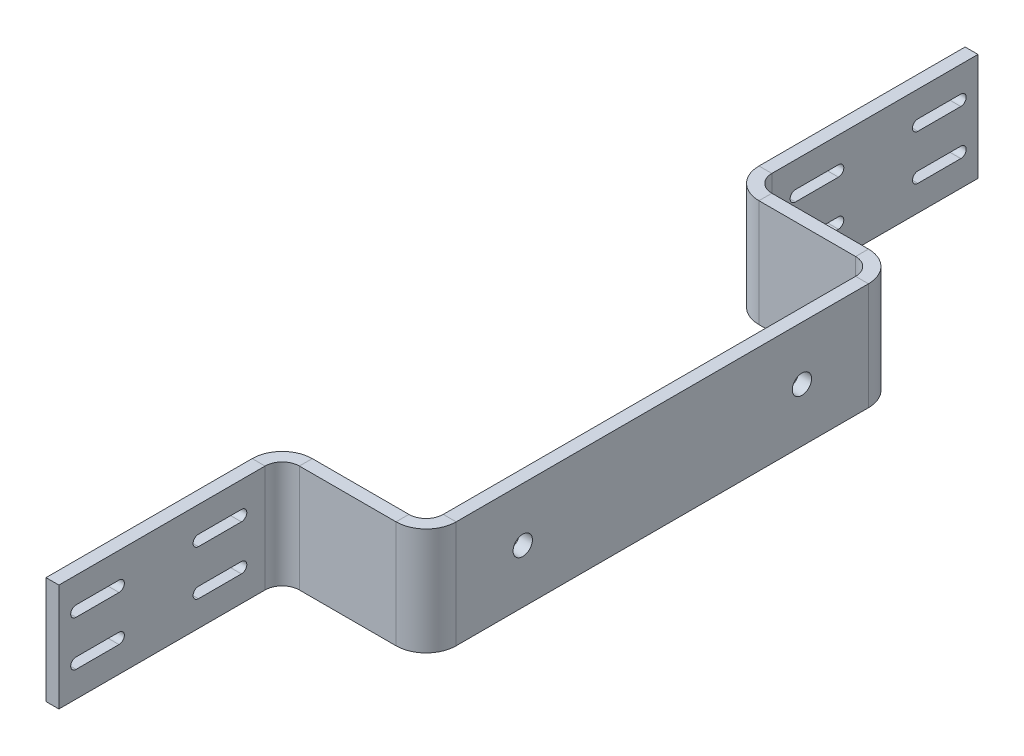
SolidWorks part; units mm, degrees
note: The reader was unsure of these and kept them because the rebuilt part matched: flange length of "Edge-Flange1", "Edge-Flange2".
material "Plain Carbon Steel"
ref_plane "Front Plane" through (0, 0, 0) normal (0, 0, 1) x (1, 0, 0)
ref_plane "Top Plane" through (0, 0, 0) normal (0, 1, 0) x (1, 0, 0)
ref_plane "Right Plane" through (0, 0, 0) normal (1, 0, 0) x (0, 0, -1)
sketch "Sketch1" plane through (0, 0, 0) normal (1, 0, 0) x (0, 0, -1)
  line L1 (-55, -25) -> (55, -25)
  line L2 (-55, -25) -> (-55, 25)
  line L3 (-55, 25) -> (55, 25)
  line L4 (55, -25) -> (55, 25)
  line L5 (-55, -25) -> (55, 25) construction
  line L6 (-55, 25) -> (55, -25) construction
  point P0 (0, 0)
  dimension "D1" = 50
  dimension "D2" = 110
base flange "Base-Flange1" sketch "Sketch1" thickness 6 reverse thickness direction no parameters "D1"=15
sketch "Sketch5" plane through (-6, 0, 0) normal (-1, 0, 0) x (0, 0, 1)
  line L0 (-30, 10.5) -> (-10, 10.5) construction
  line L3 (-30, 13) -> (-10, 13)
  line L4 (-30, 8) -> (-10, 8)
  line L6 (-55, -25) -> (-55, 25) construction
  arc A2 (-30, 13) -> (-30, 8) centre (-30, 10.5) ccw
  arc A3 (-10, 8) -> (-10, 13) centre (-10, 10.5) ccw
  point P2 (-20, 10.5)
  dimension "D1" = 20
  dimension "D2" = 5
  dimension "D3" = 10.5
  dimension "D4" = 25
extrude "Cut-Extrude1" cut sketch "Sketch5" against normal blind 10
pattern_linear "LPattern1" count 2 spacing 57 along (0, 0, 1) of "Cut-Extrude1"
mirror "Mirror1" about plane through (0, 0, 0) normal (0, 1, 0) of "LPattern1", "Cut-Extrude1"
edge flange "Edge-Flange1" sketch "Sketch11" flange angle 90 flange length 73 flange position material inside bend radius 8 thickness 6 relief rectangular parameters "D6"=10
bend "EdgeBend3" bend radius 8 bend angle 90 parameters "D5"=1
sketch "Sketch11" plane through (0, 0, -55) normal (0, 0, -1) x (0, 1, 0)
  line L1 (-25, 0) -> (25, 0) construction
  line L2 (25, 0) -> (25, 67)
  line L3 (25, 67) -> (-25, 67)
  line L4 (-25, 67) -> (-25, 0)
  line L5 (-25, 0) -> (25, 0)
edge flange "Edge-Flange2" sketch "Sketch13" flange angle 90 flange length 110 flange position material inside bend radius 8 thickness 6 relief rectangular parameters "D6"=10
bend "EdgeBend4" bend radius 8 bend angle 90 parameters "D5"=2
sketch "Sketch13" plane through (67, 0, -55) normal (1, 0, 0) x (0, -1, 0)
  line L0 (-25, 0) -> (25, 0) construction
  line L1 (-25, 0) -> (25, 0)
  line L2 (-25, 0) -> (-25, 104)
  line L3 (-25, 104) -> (25, 104)
  line L4 (25, 104) -> (25, 0)
sketch "Sketch9" plane through (61, 0, 0) normal (-1, 0, 0) x (0, 0, 1)
  line L2 (-159, -25) -> (-159, 25) construction
  circle A0 centre (-94, 0) radius 4.5
  dimension "D1" = 9
  dimension "D2" = 65
extrude "Cut-Extrude2" cut sketch "Sketch9" against normal blind 10
ref_plane "Plane1" through (0, 0, -159) normal (0, 0, -1) x (-1, 0, 0)
mirror "Mirror2" about plane through (67, 25, -159) normal (0, 0, 1) of bodies 111
bend "MirrorBend3" bend radius 8 bend angle 90 parameters "D5"=3
bend "MirrorBend4" bend radius 8 bend angle 90 parameters "D5"=4
sketch "Bend-Lines1" [suppressed] plane through (0, 0, 0) normal (0, 1, 0) x (1, 0, 0)
sketch "Bounding-Box1" [suppressed] plane through (0, 0, 0) normal (0, 1, 0) x (1, 0, 0)
sheet metal parameters "Sheet-Metal2" thickness 6 parameters "D1"=15
flat pattern "Flat-Pattern2" [suppressed]
sketch "Bend-Lines2" plane through (0, 0, 0) normal (0, 1, 0) x (1, 0, 0)
sketch3d "Bounding-Box2" [suppressed]
  line L0 (55, -25, 0) -> (-55, -25, 0) construction
  line L1 (55, 25, 0) -> (-55, 25, 0) construction
  line L2 (55, -25, 0) -> (55, 25, 0) construction
  line L3 (-55, -25, 0) -> (-55, 25, 0) construction
sheet metal parameters "Sheet-Metal5" thickness 6 parameters "D1"=15
flat pattern "Flat-Pattern2"
sketch "Bend-Lines2" plane through (0, 0, 0) normal (1, 0, 0) x (0, 0, -1)
  line L2 (48.1372, -25) -> (48.1372, 25) construction
  line L3 (48.1372, -25) -> (48.1372, 25) construction
  point P0 (-48.1372, 25)
  point P1 (-48.1372, -25)
sketch3d "Bounding-Box2" [suppressed]
  line L0 (126.2743, -25, 0) -> (-55, -25, 0) construction
  line L1 (126.2743, 25, 0) -> (-55, 25, 0) construction
  line L2 (126.2743, -25, 0) -> (126.2743, 25, 0) construction
  line L3 (-55, -25, 0) -> (-55, 25, 0) construction
bend of the flat pattern "Flatten-<EdgeBend3>1"
sheet metal parameters "Sheet-Metal7" thickness 6 parameters "D1"=15
flat pattern "Flat-Pattern2"
sketch "Bend-Lines2" plane through (0, 0, 0) normal (1, 0, 0) x (0, 0, -1)
  line L0 (-28.1372, 50) -> (-28.1372, -50) construction
  line L1 (-28.1372, 50) -> (-28.1372, -50) construction
sketch3d "Bounding-Box2" [suppressed]
  line L0 (35, -50, 0) -> (-192.2743, -50, 0) construction
  line L1 (35, 50, 0) -> (-192.2743, 50, 0) construction
  line L2 (35, -50, 0) -> (35, 50, 0) construction
  line L3 (-192.2743, -50, 0) -> (-192.2743, 50, 0) construction
sheet metal parameters "Sheet-Metal8" thickness 6 parameters "D1"=15
flat pattern "Flat-Pattern2"
sketch "Bend-Lines2" plane through (0, 0, 0) normal (1, 0, 0) x (0, 0, -1)
  line L0 (-43.1372, 17.5) -> (-43.1372, -17.5) construction
  line L1 (-43.1372, 17.5) -> (-43.1372, -17.5) construction
sketch3d "Bounding-Box2" [suppressed]
  line L0 (50, -17.5, 0) -> (-207.2743, -17.5, 0) construction
  line L1 (50, 17.5, 0) -> (-207.2743, 17.5, 0) construction
  line L2 (50, -17.5, 0) -> (50, 17.5, 0) construction
  line L3 (-207.2743, -17.5, 0) -> (-207.2743, 17.5, 0) construction
sheet metal parameters "Sheet-Metal10" thickness 6 parameters "D1"=15
flat pattern "Flat-Pattern2" [suppressed]
sketch "Bend-Lines2" plane through (0, 0, 0) normal (1, 0, 0) x (0, 0, -1)
  line L0 (-23.1372, 40) -> (-23.1372, -40) construction
  line L1 (-23.1372, 40) -> (-23.1372, -40) construction
  line L2 (-180.4115, 40) -> (-180.4115, -40) construction
  line L3 (-180.4115, 40) -> (-180.4115, -40) construction
sketch3d "Bounding-Box2" [suppressed]
  line L0 (30, -40, 0) -> (-233.5487, -40, 0) construction
  line L1 (30, 40, 0) -> (-233.5487, 40, 0) construction
  line L2 (30, -40, 0) -> (30, 40, 0) construction
  line L3 (-233.5487, -40, 0) -> (-233.5487, 40, 0) construction
bend of the flat pattern "Flatten-<EdgeBend3>2"
bend of the flat pattern "Flatten-<EdgeBend4>1"
sheet metal parameters "Sheet-Metal11" thickness 6 parameters "D1"=15
flat pattern "Flat-Pattern2"
sketch "Bend-Lines2" plane through (0, 0, 0) normal (1, 0, 0) x (0, 0, -1)
  line L4 (119.4115, -25) -> (119.4115, 25) construction
  line L5 (48.1372, -25) -> (48.1372, 25) construction
  line L6 (119.4115, -25) -> (119.4115, 25) construction
  line L7 (48.1372, -25) -> (48.1372, 25) construction
sketch3d "Bounding-Box2" [suppressed]
  line L0 (337.5487, -25, 0) -> (-55, -25, 0) construction
  line L1 (337.5487, 25, 0) -> (-55, 25, 0) construction
  line L2 (337.5487, -25, 0) -> (337.5487, 25, 0) construction
  line L3 (-55, -25, 0) -> (-55, 25, 0) construction
bend of the flat pattern "Flatten-<EdgeBend3>3"
bend of the flat pattern "Flatten-<EdgeBend4>2"
sheet metal parameters "Sheet-Metal14" thickness 6 parameters "D1"=15
flat pattern "Flat-Pattern2"
sketch "Bend-Lines2" plane through (0, 0, 0) normal (1, 0, 0) x (0, 0, -1)
  line L0 (-48.1372, -25) -> (-48.1372, 25) construction
  line L1 (-48.1372, -25) -> (-48.1372, 25) construction
  line L2 (-119.4115, 25) -> (-119.4115, -25) construction
  line L3 (-119.4115, 25) -> (-119.4115, -25) construction
sketch3d "Bounding-Box2" [suppressed]
  line L0 (55, -25, 0) -> (-337.5487, -25, 0) construction
  line L1 (55, 25, 0) -> (-337.5487, 25, 0) construction
  line L2 (55, -25, 0) -> (55, 25, 0) construction
  line L3 (-337.5487, -25, 0) -> (-337.5487, 25, 0) construction
sheet metal parameters "Sheet-Metal15" thickness 6 parameters "D1"=15
flat pattern "Flat-Pattern15"
sketch "Bend-Lines3" plane through (0, 0, 0) normal (1, 0, 0) x (0, 0, -1)
  line L8 (321.1969, -25) -> (321.1969, 25) construction
  line L9 (383.4757, -25) -> (383.4757, 25) construction
  line L10 (111.9181, -25) -> (111.9181, 25) construction
  line L11 (49.6394, -25) -> (49.6394, 25) construction
  line L12 (321.1969, -25) -> (321.1969, 25) construction
  line L13 (383.4757, -25) -> (383.4757, 25) construction
  line L14 (111.9181, -25) -> (111.9181, 25) construction
  line L15 (49.6394, -25) -> (49.6394, 25) construction
sketch3d "Bounding-Box3" [suppressed]
  line L0 (488.115, -25, 0) -> (-55, -25, 0) construction
  line L1 (488.115, 25, 0) -> (-55, 25, 0) construction
  line L2 (488.115, -25, 0) -> (488.115, 25, 0) construction
  line L3 (-55, -25, 0) -> (-55, 25, 0) construction
bend of the flat pattern "Flatten-<EdgeBend4>3"
bend of the flat pattern "Flatten-<EdgeBend3>4"
bend of the flat pattern "Flatten-<MirrorBend3>1"
bend of the flat pattern "Flatten-<MirrorBend4>1"
